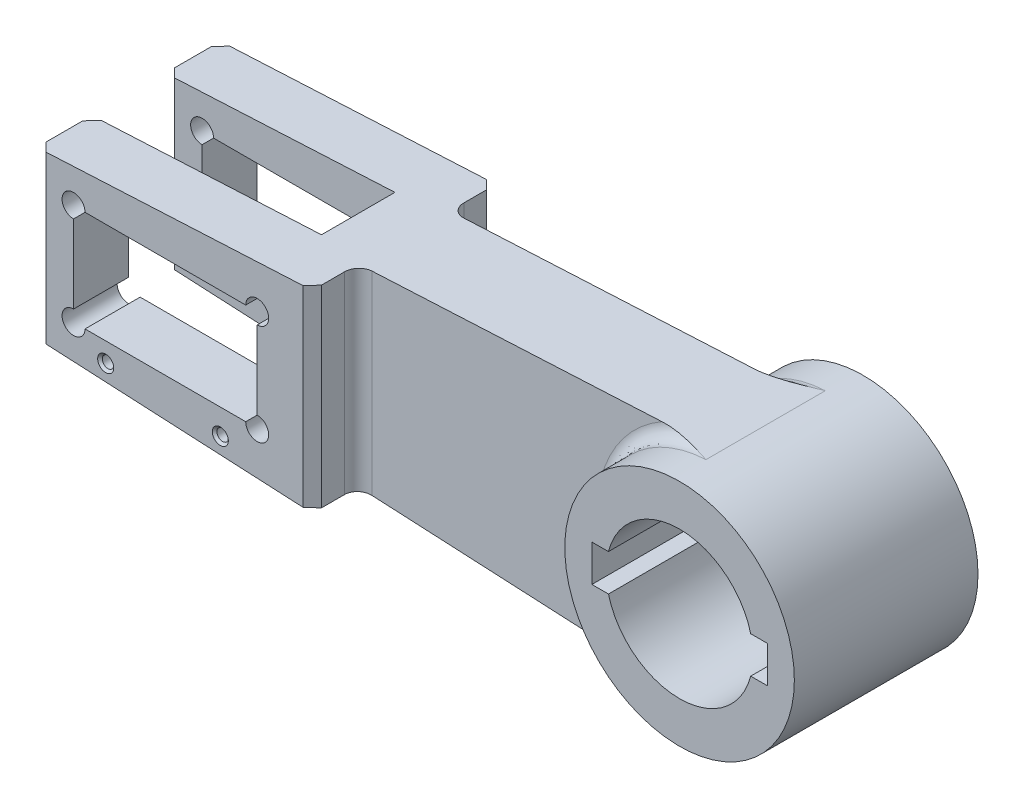
SolidWorks part; units mm, degrees
material "Простая углеродистая сталь"
ref_plane "Спереди" through (0, 0, 0) normal (0, 0, 1) x (1, 0, 0)
ref_plane "Сверху" through (0, 0, 0) normal (0, 1, 0) x (1, 0, 0)
ref_plane "Справа" through (0, 0, 0) normal (1, 0, 0) x (0, 0, -1)
sketch "Эскиз1" plane through (0, 0, 0) normal (0, 0, 1) x (1, 0, 0)
  line L0 (0, 0) -> (-170.2173, 0) construction
  line L1 (-1.254, 24.9685) -> (-80, 21.0135)
  line L2 (19.1, -4) -> (-19.1, -4)
  line L3 (19.1, -4) -> (19.1, 4)
  line L4 (19.1, 4) -> (-19.1, 4)
  line L5 (-19.1, -4) -> (-19.1, 4)
  line L6 (19.1, -4) -> (-19.1, 4) construction
  line L7 (19.1, 4) -> (-19.1, -4) construction
  line L8 (-80, 21.0135) -> (-80, -21.0135)
  line L9 (-80, -21.0135) -> (-1.254, -24.9685)
  line L10 (-80, 21.0135) -> (-140, 18)
  line L11 (-140, 18) -> (-140, -18)
  line L12 (-140, -18) -> (-80, -21.0135)
  line L13 (-90, 20.5113) -> (-90, -20.5113)
  line L14 (-132, -11) -> (-92, -11)
  line L15 (-132, -11) -> (-132, 11)
  line L16 (-132, 11) -> (-92, 11)
  line L17 (-92, -11) -> (-92, 11)
  line L18 (-132, -11) -> (-92, 11) construction
  line L19 (-132, 11) -> (-92, -11) construction
  circle A0 centre (0, 0) radius 25
  circle A1 centre (0, 0) radius 16
  circle A2 centre (-132, 11) radius 2.5
  circle A3 centre (-92, 11) radius 2.5
  circle A4 centre (-92, -11) radius 2.5
  circle A5 centre (-132, -11) radius 2.5
  point P11 (-80, 0)
  point P14 (-112, 0)
  dimension "D1" = 50
  dimension "D5" = 32
  dimension "D8" = 5
  dimension "D2" = 165
  dimension "D3" = 36
  dimension "D4" = 55
  dimension "D6" = 8
  dimension "D7" = 38.2
  dimension "D9" = 22
  dimension "D10" = 40
  dimension "D11" = 8
  dimension "D12" = 50
extrude "Бобышка-Вытянуть1" add sketch "Эскиз1" along normal mid plane 20 contours A5 L15 A2 L16 A3 L13 L10 L11 L12 A4 L14 | A4 L13 L12 L8 L10 A3 | A0 L1 L8 L9 | A0 A1 L4 L3 L2 L5 region at (-49.0933, 0, 0) region at (16.7413, 17.6032, 0) region at (-84.956, 0, 0) region at (-90.6467, 16.5056, 0)
extrude "Бобышка-Вытянуть2" add sketch "Эскиз1<3>" along normal mid plane 40 contours A5 L15 A2 L16 A3 L13 L10 L11 L12 A4 L14 | A4 L13 L12 L8 L10 A3 | A0 A1 L4 L3 L2 L5 | A4 L13 A3 L17 region at (16.7413, 17.6032, 0) region at (-84.956, 0, 0) region at (-90.6467, 16.5056, 0) region at (-90.9821, 0, 0)
sketch "Эскиз1<3>" plane through (0, 0, 0) normal (0, 0, 1) x (1, 0, 0) same geometry as "Эскиз1"
extrude "Вырез-Вытянуть1" cut sketch "Эскиз1<4>" against normal mid plane 16 contours A5 L15 A2 L16 A3 L13 L10 L11 L12 A4 L14 | A4 L13 A3 L17 region at (-90.6467, 16.5056, 0) region at (-90.9821, 0, 0)
sketch "Эскиз1<4>" plane through (0, 0, 0) normal (0, 0, 1) x (1, 0, 0) same geometry as "Эскиз1"
fillet "Скругление1" radius 3 4 edges at (-80, 0, -10) (-80, 0, 10) (-25, 0, -10) (-25, 0, 10)
chamfer "Фаска1" distance 2 angle 45 6 edges at (-140, 0, 8) (-140, 0, -8) (-140, 0, -20) (-140, 0, 20) (-80, 0, 20) (-80, 0, -20)
hole_wizard "Отверстие обработанное метчиком M31" positions "Эскиз3" profile "Эскиз2" tap size "M3" standard "Iso"
sketch "Эскиз3" plane through (0, 0, 20) normal (0, 0, 1) x (1, 0, 0)
  line L0 (-140, -18) -> (-140, 18) construction
  line L1 (-138, -18.1005) -> (-82, -20.9131) construction
  point P0 (-125, -15.249)
  point P2 (-100.0315, -16.503)
  dimension "D1" = 25
  dimension "D2" = 15
  dimension "D3" = 3.5
  dimension "D4" = 3.5
sketch "Эскиз2" plane through (-125, -15.249, 20) normal (1, 0, 0) x (0, -1, 0)
  line L0 (0, 0) -> (0, 10.7511)
  line L1 (0, 10.7511) -> (1.25, 10)
  line L2 (1.25, 10) -> (1.25, 0)
  line L5 (1.25, 0) -> (0, 0)
  line L10 (0, 10.7511) -> (-1.25, 10) construction
  line L11 (0, -6.35) -> (0, 107.95) construction
  dimension "Диаметр сверла" = 2.5
  dimension "Глубина сверла" = 10
  dimension "Угол заточки сверла" = 118
cosmetic thread "Отверстие резьбы1" parameters "D1"=8, "D2"=3
cosmetic thread "Отверстие резьбы2" parameters "D1"=8, "D2"=3
chamfer "Фаска2" distance 0.5 angle 45 2 edges at (-123.75, -15.249, 20) (-98.7815, -16.503, 20)
